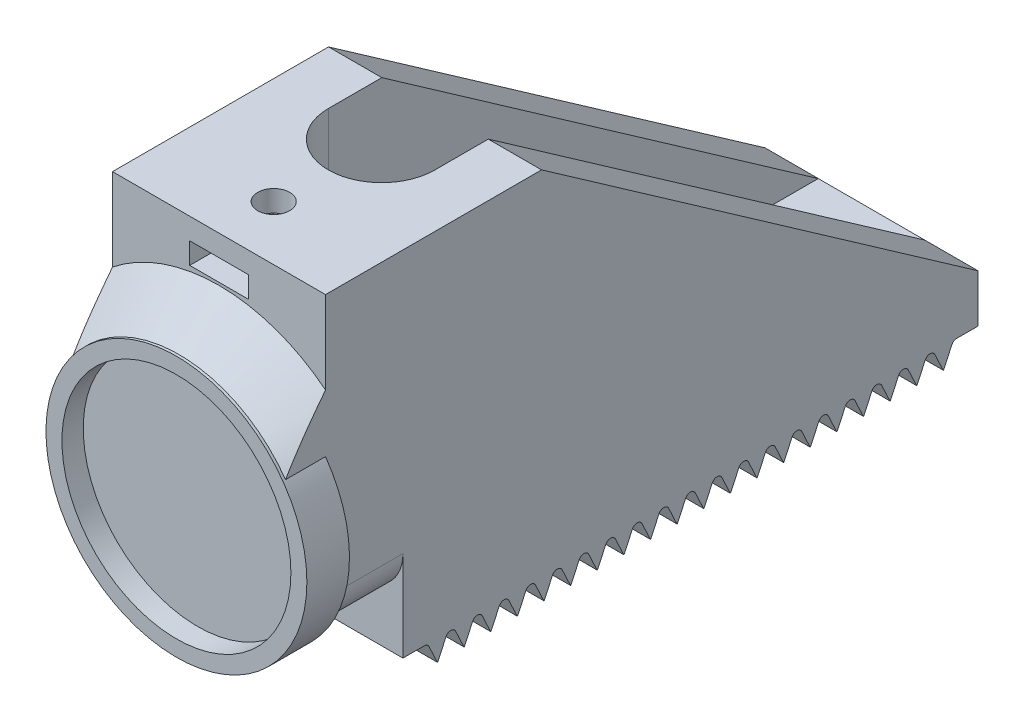
SolidWorks part; units mm, degrees
note: The reader was unsure of these and kept them because the rebuilt part matched: shared geometry of "Sketch4<3>", "Sketch5<2>".
ref_plane "Front Plane" through (0, 0, 0) normal (0, 0, 1) x (1, 0, 0)
ref_plane "Top Plane" through (0, 0, 0) normal (0, 1, 0) x (1, 0, 0)
ref_plane "Right Plane" through (0, 0, 0) normal (1, 0, 0) x (0, 0, -1)
sketch "Sketch1" plane through (0, 0, 0) normal (0, 0, 1) x (1, 0, 0)
  circle A0 centre (0, 0) radius 12.25
  dimension "D1" = 24.5
extrude "Boss-Extrude1" add sketch "Sketch1" along normal blind 2
sketch "Sketch2" plane through (0, 0, 2) normal (0, 0, 1) x (1, 0, 0)
  line L0 (0, 10.75) -> (0, 12.25) construction
  circle A0 centre (0, 0) radius 10.5 construction
  circle A1 centre (0, 0) radius 12.25
  circle A2 centre (0, 0) radius 12.25
  circle A3 centre (0, 0) radius 10.75
  dimension "D2" = 21
  dimension "D4" = 1.5
extrude "Boss-Extrude2" add sketch "Sketch2" along normal blind 2
sketch "Sketch3" plane through (0, 0, 0) normal (1, 0, 0) x (0, 0, -1)
  line L6 (57.9953, -14.8943) -> (57.2219, -13.2357)
  line L7 (58.8156, -13.2357) -> (58.0421, -14.8943)
  line L8 (57.9953, -14.8943) -> (57.2219, -13.2357)
  line L9 (58.8156, -13.2357) -> (58.0421, -14.8943)
  line L10 (56.3156, -13.2357) -> (55.5421, -14.8943)
  line L11 (55.4953, -14.8943) -> (54.7219, -13.2357)
  line L12 (53.8156, -13.2357) -> (53.0421, -14.8943)
  line L13 (52.9953, -14.8943) -> (52.2219, -13.2357)
  line L14 (51.3156, -13.2357) -> (50.5421, -14.8943)
  line L15 (50.4953, -14.8943) -> (49.7219, -13.2357)
  line L16 (48.8156, -13.2357) -> (48.0421, -14.8943)
  line L17 (47.9953, -14.8943) -> (47.2219, -13.2357)
  line L18 (46.3156, -13.2357) -> (45.5421, -14.8943)
  line L19 (45.4953, -14.8943) -> (44.7219, -13.2357)
  line L20 (43.8156, -13.2357) -> (43.0421, -14.8943)
  line L21 (42.9953, -14.8943) -> (42.2219, -13.2357)
  line L22 (41.3156, -13.2357) -> (40.5421, -14.8943)
  line L23 (40.4953, -14.8943) -> (39.7219, -13.2357)
  line L24 (38.8156, -13.2357) -> (38.0421, -14.8943)
  line L25 (37.9953, -14.8943) -> (37.2219, -13.2357)
  line L26 (36.3156, -13.2357) -> (35.5421, -14.8943)
  line L27 (35.4953, -14.8943) -> (34.7219, -13.2357)
  line L28 (33.8156, -13.2357) -> (33.0421, -14.8943)
  line L29 (32.9953, -14.8943) -> (32.2219, -13.2357)
  line L30 (31.3156, -13.2357) -> (30.5421, -14.8943)
  line L31 (30.4953, -14.8943) -> (29.7219, -13.2357)
  line L32 (28.8156, -13.2357) -> (28.0421, -14.8943)
  line L33 (27.9953, -14.8943) -> (27.2219, -13.2357)
  line L34 (26.3156, -13.2357) -> (25.5421, -14.8943)
  line L35 (25.4953, -14.8943) -> (24.7219, -13.2357)
  line L36 (23.8156, -13.2357) -> (23.0421, -14.8943)
  line L37 (22.9953, -14.8943) -> (22.2219, -13.2357)
  line L38 (21.3156, -13.2357) -> (20.5421, -14.8943)
  line L39 (20.4953, -14.8943) -> (19.7219, -13.2357)
  line L40 (18.8156, -13.2357) -> (18.0421, -14.8943)
  line L41 (17.9953, -14.8943) -> (17.2219, -13.2357)
  line L42 (16.3156, -13.2357) -> (15.5421, -14.8943)
  line L43 (15.4953, -14.8943) -> (14.7219, -13.2357)
  line L44 (13.8156, -13.2357) -> (13.0421, -14.8943)
  line L45 (12.9953, -14.8943) -> (12.2219, -13.2357)
  line L46 (11.3156, -13.2357) -> (10.5421, -14.8943)
  line L47 (10.4953, -14.8943) -> (9.7219, -13.2357)
  line L48 (59.2687, -12.947) -> (56.7687, -12.947) construction
  line L49 (9.2687, -12.947) -> (7.2687, -12.947)
  line L50 (7.2687, -12.947) -> (7.2687, -10.447)
  line L51 (7.2687, -10.447) -> (61.2687, -10.447)
  line L52 (61.2687, -10.447) -> (61.2687, -12.947)
  line L53 (61.2687, -12.947) -> (59.2687, -12.947)
  arc A3 (56.7687, -12.947) -> (56.3156, -13.2357) centre (56.7687, -13.447) ccw
  arc A4 (55.4953, -14.8943) -> (55.5421, -14.8943) centre (55.5187, -14.8834) ccw
  arc A5 (54.7219, -13.2357) -> (54.2687, -12.947) centre (54.2687, -13.447) ccw
  arc A6 (57.2219, -13.2357) -> (56.3156, -13.2357) centre (56.7687, -13.447) ccw
  arc A7 (59.7219, -13.2357) -> (58.8156, -13.2357) centre (59.2687, -13.447) ccw
  arc A8 (57.2219, -13.2357) -> (56.7687, -12.947) centre (56.7687, -13.447) ccw
  arc A9 (59.2687, -12.947) -> (58.8156, -13.2357) centre (59.2687, -13.447) ccw
  arc A10 (57.9953, -14.8943) -> (58.0421, -14.8943) centre (58.0187, -14.8834) ccw
  arc A11 (57.9953, -14.8943) -> (58.0421, -14.8943) centre (58.0187, -14.8834) ccw
  arc A12 (54.2687, -12.947) -> (53.8156, -13.2357) centre (54.2687, -13.447) ccw
  arc A13 (52.9953, -14.8943) -> (53.0421, -14.8943) centre (53.0187, -14.8834) ccw
  arc A14 (52.2219, -13.2357) -> (51.7687, -12.947) centre (51.7687, -13.447) ccw
  arc A15 (51.7687, -12.947) -> (51.3156, -13.2357) centre (51.7687, -13.447) ccw
  arc A16 (50.4953, -14.8943) -> (50.5421, -14.8943) centre (50.5187, -14.8834) ccw
  arc A17 (49.7219, -13.2357) -> (49.2687, -12.947) centre (49.2687, -13.447) ccw
  arc A18 (49.2687, -12.947) -> (48.8156, -13.2357) centre (49.2687, -13.447) ccw
  arc A19 (47.9953, -14.8943) -> (48.0421, -14.8943) centre (48.0187, -14.8834) ccw
  arc A20 (47.2219, -13.2357) -> (46.7687, -12.947) centre (46.7687, -13.447) ccw
  arc A21 (46.7687, -12.947) -> (46.3156, -13.2357) centre (46.7687, -13.447) ccw
  arc A22 (45.4953, -14.8943) -> (45.5421, -14.8943) centre (45.5187, -14.8834) ccw
  arc A23 (44.7219, -13.2357) -> (44.2687, -12.947) centre (44.2687, -13.447) ccw
  arc A24 (44.2687, -12.947) -> (43.8156, -13.2357) centre (44.2687, -13.447) ccw
  arc A25 (42.9953, -14.8943) -> (43.0421, -14.8943) centre (43.0187, -14.8834) ccw
  arc A26 (42.2219, -13.2357) -> (41.7687, -12.947) centre (41.7687, -13.447) ccw
  arc A27 (41.7687, -12.947) -> (41.3156, -13.2357) centre (41.7687, -13.447) ccw
  arc A28 (40.4953, -14.8943) -> (40.5421, -14.8943) centre (40.5187, -14.8834) ccw
  arc A29 (39.7219, -13.2357) -> (39.2687, -12.947) centre (39.2687, -13.447) ccw
  arc A30 (39.2687, -12.947) -> (38.8156, -13.2357) centre (39.2687, -13.447) ccw
  arc A31 (37.9953, -14.8943) -> (38.0421, -14.8943) centre (38.0187, -14.8834) ccw
  arc A32 (37.2219, -13.2357) -> (36.7687, -12.947) centre (36.7687, -13.447) ccw
  arc A33 (36.7687, -12.947) -> (36.3156, -13.2357) centre (36.7687, -13.447) ccw
  arc A34 (35.4953, -14.8943) -> (35.5421, -14.8943) centre (35.5187, -14.8834) ccw
  arc A35 (34.7219, -13.2357) -> (34.2687, -12.947) centre (34.2687, -13.447) ccw
  arc A36 (34.2687, -12.947) -> (33.8156, -13.2357) centre (34.2687, -13.447) ccw
  arc A37 (32.9953, -14.8943) -> (33.0421, -14.8943) centre (33.0187, -14.8834) ccw
  arc A38 (32.2219, -13.2357) -> (31.7687, -12.947) centre (31.7687, -13.447) ccw
  arc A39 (31.7687, -12.947) -> (31.3156, -13.2357) centre (31.7687, -13.447) ccw
  arc A40 (30.4953, -14.8943) -> (30.5421, -14.8943) centre (30.5187, -14.8834) ccw
  arc A41 (29.7219, -13.2357) -> (29.2687, -12.947) centre (29.2687, -13.447) ccw
  arc A42 (29.2687, -12.947) -> (28.8156, -13.2357) centre (29.2687, -13.447) ccw
  arc A43 (27.9953, -14.8943) -> (28.0421, -14.8943) centre (28.0187, -14.8834) ccw
  arc A44 (27.2219, -13.2357) -> (26.7687, -12.947) centre (26.7687, -13.447) ccw
  arc A45 (26.7687, -12.947) -> (26.3156, -13.2357) centre (26.7687, -13.447) ccw
  arc A46 (25.4953, -14.8943) -> (25.5421, -14.8943) centre (25.5187, -14.8834) ccw
  arc A47 (24.7219, -13.2357) -> (24.2687, -12.947) centre (24.2687, -13.447) ccw
  arc A48 (24.2687, -12.947) -> (23.8156, -13.2357) centre (24.2687, -13.447) ccw
  arc A49 (22.9953, -14.8943) -> (23.0421, -14.8943) centre (23.0187, -14.8834) ccw
  arc A50 (22.2219, -13.2357) -> (21.7687, -12.947) centre (21.7687, -13.447) ccw
  arc A51 (21.7687, -12.947) -> (21.3156, -13.2357) centre (21.7687, -13.447) ccw
  arc A52 (20.4953, -14.8943) -> (20.5421, -14.8943) centre (20.5187, -14.8834) ccw
  arc A53 (19.7219, -13.2357) -> (19.2687, -12.947) centre (19.2687, -13.447) ccw
  arc A54 (19.2687, -12.947) -> (18.8156, -13.2357) centre (19.2687, -13.447) ccw
  arc A55 (17.9953, -14.8943) -> (18.0421, -14.8943) centre (18.0187, -14.8834) ccw
  arc A56 (17.2219, -13.2357) -> (16.7687, -12.947) centre (16.7687, -13.447) ccw
  arc A57 (16.7687, -12.947) -> (16.3156, -13.2357) centre (16.7687, -13.447) ccw
  arc A58 (15.4953, -14.8943) -> (15.5421, -14.8943) centre (15.5187, -14.8834) ccw
  arc A59 (14.7219, -13.2357) -> (14.2687, -12.947) centre (14.2687, -13.447) ccw
  arc A60 (14.2687, -12.947) -> (13.8156, -13.2357) centre (14.2687, -13.447) ccw
  arc A61 (12.9953, -14.8943) -> (13.0421, -14.8943) centre (13.0187, -14.8834) ccw
  arc A62 (12.2219, -13.2357) -> (11.7687, -12.947) centre (11.7687, -13.447) ccw
  arc A63 (11.7687, -12.947) -> (11.3156, -13.2357) centre (11.7687, -13.447) ccw
  arc A64 (10.4953, -14.8943) -> (10.5421, -14.8943) centre (10.5187, -14.8834) ccw
  arc A65 (9.7219, -13.2357) -> (9.2687, -12.947) centre (9.2687, -13.447) ccw
  dimension "D2" = 2
  dimension "D3" = 2.5
  dimension "D4" = 2
extrude "Boss-Extrude3" add sketch "Sketch3" along normal mid plane 20 separate body
sketch "Sketch4" plane through (0, -10.447, 0) normal (0, 1, 0) x (1, 0, 0)
  line L0 (0, 53.2687) -> (0, 15.2687) construction
  line L1 (5, 53.2687) -> (5, 15.2687)
  line L2 (-5, 53.2687) -> (-5, 15.2687)
  line L3 (4, 53.2687) -> (5, 53.2687) construction
  line L4 (0, 58.2687) -> (0, 61.2687) construction
  line L5 (10, 61.2687) -> (-10, 61.2687) construction
  line L6 (0, 10.2687) -> (0, 7.2687) construction
  line L7 (10, 7.2687) -> (-10, 7.2687) construction
  line L8 (0, 53.2687) -> (0, 15.2687) construction
  line L9 (2.75, 53.2687) -> (2.75, 15.2687)
  line L10 (-2.75, 53.2687) -> (-2.75, 15.2687)
  line L11 (2.5, 53.2687) -> (2.75, 53.2687) construction
  line L12 (-10, 61.2687) -> (-10, 7.2687)
  line L13 (-10, 7.2687) -> (10, 7.2687)
  line L14 (10, 7.2687) -> (10, 61.2687)
  line L15 (10, 61.2687) -> (-10, 61.2687)
  line L16 (-10, 61.2687) -> (-10, 7.2687)
  line L17 (-10, 7.2687) -> (10, 7.2687)
  line L18 (10, 7.2687) -> (10, 61.2687)
  line L19 (10, 61.2687) -> (-10, 61.2687)
  arc A0 (5, 53.2687) -> (-5, 53.2687) centre (0, 53.2687) ccw
  arc A1 (-5, 15.2687) -> (5, 15.2687) centre (0, 15.2687) ccw
  circle A2 centre (0, 53.2687) radius 4 construction
  arc A3 (2.75, 53.2687) -> (-2.75, 53.2687) centre (0, 53.2687) ccw
  arc A4 (-2.75, 15.2687) -> (2.75, 15.2687) centre (0, 15.2687) ccw
  circle A5 centre (0, 53.2687) radius 2.5 construction
  point P3 (0, 34.2687)
  point P22 (0, 34.2687)
  line M7 (-10, 61.2687) -> (-10, 7.2687)
  line M8 (-10, 7.2687) -> (10, 7.2687)
  line M9 (10, 7.2687) -> (10, 61.2687)
  line M10 (10, 61.2687) -> (-10, 61.2687)
  dimension "D1" = 8
  dimension "D5" = 5
  dimension "D2" = 1
  dimension "D3" = 3
  dimension "D6" = 0.25
extrude "Boss-Extrude4" add sketch "Sketch4" along normal blind 2 contours A1 L2 A0 L1 M10 M7 M8 M9
extrude "Cut-Extrude1" cut sketch "Sketch4<3>" against normal up to next contours L10 A4 L9 A3
sketch "Sketch4<3>" plane through (0, -10.447, 0) normal (0, 1, 0) x (1, 0, 0) same geometry as "Sketch4"
sketch "Sketch5" plane through (-10, 0, 0) normal (-1, 0, 0) x (0, 0, 1)
  line L0 (-61.2687, -8.447) -> (-20.2851, 20.25)
  line L1 (-20.2851, 20.25) -> (0, 20.25)
  line L2 (0, 20.25) -> (0, 12.25)
  line L3 (0, -8.447) -> (-7.2687, -8.447)
  line L4 (-7.2687, -8.447) -> (-61.2687, -8.447)
  line L5 (0, 12.25) -> (0, -12.25) construction
  line L6 (0, 12.25) -> (0, -8.447)
  line L7 (4, 12.25) -> (0, 12.25) construction
  dimension "D1" = 8
  dimension "D2" = 35
extrude "Boss-Extrude6" add sketch "Sketch5" against normal up to surface (107 mm away)
extrude "Boss-Extrude7" add sketch "Sketch5<2>" along normal up to surface (5 mm away) from surface at -20 up to face at (5, -9.447, -34.2687) starting at face at (10, -13.8205, -34.2687)
sketch "Sketch5<2>" plane through (-10, 0, 0) normal (-1, 0, 0) x (0, 0, 1) same geometry as "Sketch5"
sketch "Sketch6" plane through (0, -8.447, 0) normal (0, 1, 0) x (1, 0, 0)
  line L0 (5, 15.2687) -> (5, 0)
  line L1 (5, 0) -> (-5, 0)
  line L2 (-5, 7.2687) -> (-5, 0) construction
  line L3 (-5, 0) -> (-5, 15.2687)
  line L4 (5, 7.2687) -> (5, 0) construction
  line L5 (5, 0) -> (8.8719, 0) construction
  arc A0 (-5, 15.2687) -> (5, 15.2687) centre (0, 15.2687) ccw construction
  arc A1 (-5, 15.2687) -> (5, 15.2687) centre (0, 15.2687) ccw
extrude "Boss-Extrude8" add sketch "Sketch6" along normal up to surface (28.697 mm away) up to face at (7.5, 20.25, -10.1425)
fillet "Fillet1" radius 4 2 edges at (10, -8.447, -3.6344) (-10, -8.447, -3.6344)
chamfer "Chamfer1" distance 3.75 angle 45 1 edges at (0, 12.25, 0)
sketch "Sketch7" plane through (0, 20.25, 0) normal (0, 1, 0) x (1, 0, 0)
  line L0 (0, 10.2687) -> (0, 0) construction
  circle A0 centre (0, 5.1344) radius 1.25 construction
  circle A1 centre (0, 5.1344) radius 1.5
  arc A2 (-5, 15.2687) -> (5, 15.2687) centre (0, 15.2687) ccw construction
  point P7 (0, 5.1344)
  dimension "D1" = 2.5
  dimension "D2" = 0.25
extrude "Cut-Extrude2" cut sketch "Sketch7" against normal blind 20
ref_plane "Plane1" through (0, 18.25, 0) normal (0, 1, 0) x (1, 0, 0)
sketch "Sketch8" plane through (0, 18.25, 0) normal (0, 1, 0) x (1, 0, 0)
  line L0 (2.75, 2.3844) -> (2.75, -2)
  line L1 (-2.75, 7.8844) -> (2.75, 7.8844)
  line L2 (-2.75, 7.8844) -> (-2.75, 2.3844)
  line L3 (-2.75, 2.3844) -> (2.75, 2.3844) construction
  line L4 (2.75, 7.8844) -> (2.75, 2.3844)
  line L5 (-2.75, 7.8844) -> (2.75, 2.3844) construction
  line L6 (-2.75, 2.3844) -> (2.75, 7.8844) construction
  line L7 (2.75, -2) -> (-2.75, -2)
  line L8 (-2.75, -2) -> (-2.75, 2.3844)
  line L9 (-10.75, -2) -> (10.75, -2) construction
  point P0 (0, 5.1344)
  dimension "D1" = 5.5
extrude "Cut-Extrude3" cut sketch "Sketch8" against normal blind 2
chamfer "Chamfer2" distance 1 angle 45 1 edges at (0, 0.25, -3.6344)
equation "\"Tolerance\" = 0.25mm"
equation "\"Pocket_Head_M5\"= 8mm"
equation "\"Pocket_Head_M4\" = 7mm"
equation "\"Pocket_Nut_M4\" = 7mm"
equation "\"Pocket_Nut_M2.5\" = 5mm"
equation "\"Pocket_Nut_M5\"= 8mm"
equation "\"Pocket_Nut_M3\"= 5.5mm"
equation "\"Pocket_Head_M3\"= 5.5mm"
equation "\"Pocket_Head_M2.5\" = 4.7mm"
equation "\"Pocket_Head_M6\" = 10mm"
equation "\"D3@Sketch2\"=\"Tolerance\""
equation "\"D1@Sketch3\"=\"Tolerance\""
equation "\"D1@Sketch4\"=\"Pocket_Head_M5\""
equation "\"D6@Sketch4\"=\"Tolerance\""
equation "\"D2@Sketch7\"=\"Tolerance\""
equation "\"D1@Sketch8\"=\"Pocket_Nut_M3\""
equation "\"D1@Cut-Extrude3\"=( 1.5 + ( \"Tolerance\" * 2 ) )"
